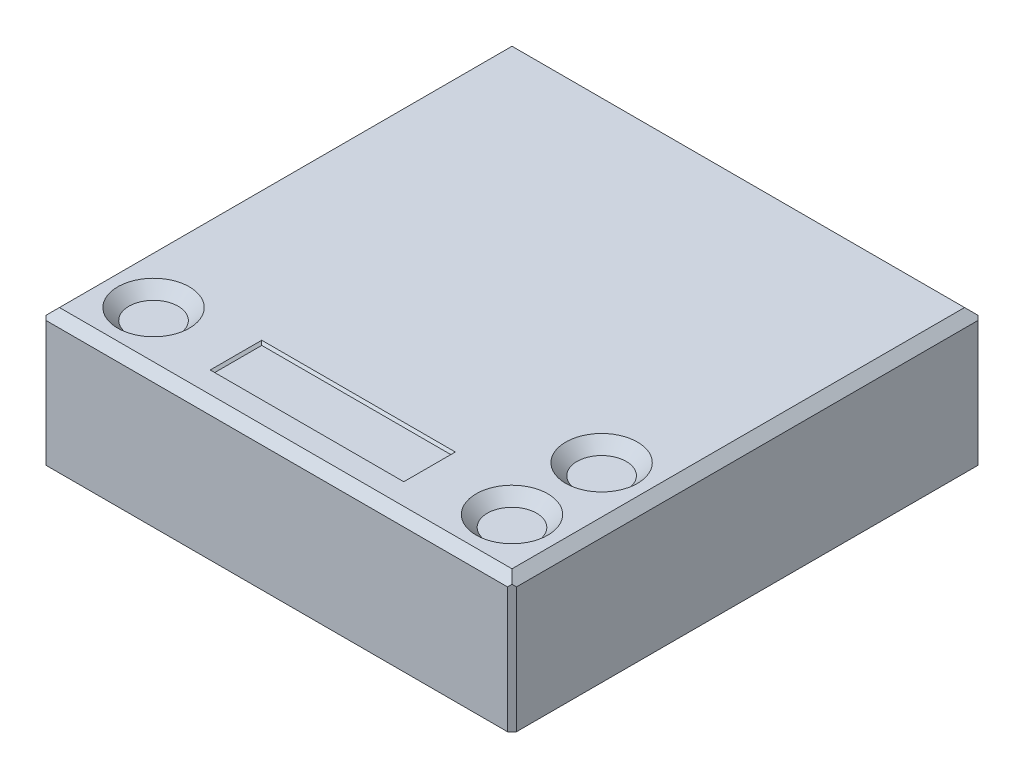
SolidWorks part; units mm, degrees
ref_plane "前视基准面" through (0, 0, 0) normal (0, 0, 1) x (1, 0, 0)
ref_plane "上视基准面" through (0, 0, 0) normal (0, 1, 0) x (1, 0, 0)
ref_plane "右视基准面" through (0, 0, 0) normal (1, 0, 0) x (0, 0, -1)
other "Configuration Table"
sketch "草图1" plane through (0, 0, 0) normal (0, 1, 0) x (1, 0, 0)
  line L0 (-45, 45) -> (45, 45) construction
  line L1 (-50, 50) -> (50, 50)
  line L2 (-50, 50) -> (-50, -50)
  line L3 (-50, -50) -> (50, -50)
  line L4 (50, 50) -> (50, -50)
  line L5 (-50, 50) -> (50, -50) construction
  line L6 (-50, -50) -> (50, 50) construction
  line L7 (-30, -30) -> (30, -30) construction
  line L8 (-40, -40) -> (40, -40) construction
  line L9 (40, -40) -> (40, -20) construction
  line L10 (0, -50) -> (0, -25) construction
  line L11 (28, -31) -> (-24, -31)
  line L12 (28, -31) -> (28, -49)
  line L13 (28, -49) -> (-24, -49)
  line L14 (-24, -31) -> (-24, -49)
  line L15 (0, -25) -> (0, -10) construction
  circle A0 centre (-45, 45) radius 1.75
  circle A1 centre (45, 45) radius 1.75
  circle A2 centre (-30, -30) radius 1.75
  circle A3 centre (30, -30) radius 1.75
  circle A4 centre (-40, -40) radius 5
  circle A5 centre (40, -40) radius 5
  circle A6 centre (40, -20) radius 5
  circle A7 centre (0, -10) radius 2.25
  circle A8 centre (0, -25) radius 2.25
  point P0 (0, 0)
  dimension "D4" = 3.5
  dimension "D8" = 10
  dimension "D13" = 4.5
  dimension "D1" = 100
  dimension "D2" = 100
  dimension "D3" = 5
  dimension "D5" = 20
  dimension "D6" = 10
  dimension "D7" = 20
  dimension "D9" = 52
  dimension "D10" = 18
  dimension "D11" = 1
  dimension "D12" = 22
  dimension "D14" = 25
  dimension "D15" = 15
sketch "草图2" plane through (0, 0, 0) normal (0, 1, 0) x (1, 0, 0)
  line L0 (50, 50) -> (50, -50) construction
  line L1 (-50.5, 50.5) -> (50.5, 50.5)
  line L2 (-50.5, 50.5) -> (-50.5, -50.5)
  line L3 (-50.5, -50.5) -> (50.5, -50.5)
  line L4 (50.5, 50.5) -> (50.5, -50.5)
  line L5 (-50.5, 50.5) -> (50.5, -50.5) construction
  line L6 (-50.5, -50.5) -> (50.5, 50.5) construction
  line L7 (-50, -50) -> (50, -50) construction
  line L9 (-52.5, 52.5) -> (52.5, 52.5)
  line L10 (-52.5, 52.5) -> (-52.5, -52.5)
  line L11 (-52.5, -52.5) -> (52.5, -52.5)
  line L12 (52.5, 52.5) -> (52.5, -52.5)
  line L13 (-52.5, 52.5) -> (52.5, -52.5) construction
  line L14 (-52.5, -52.5) -> (52.5, 52.5) construction
  point P0 (0, 0)
  point P10 (0, 0)
  dimension "D1" = 0.5
  dimension "D2" = 0.5
  dimension "D3" = 2
  dimension "D4" = 2
extrude "凸台-拉伸1" add sketch "草图2" against normal blind 25
extrude "凸台-拉伸2" add sketch "草图2<2>" along normal blind 5 contours L11 L12 L9 L10
sketch "草图2<2>" plane through (0, 0, 0) normal (0, 1, 0) x (1, 0, 0) same geometry as "草图2"
sketch "草图3" plane through (0, 0, 0) normal (0, 1, 0) x (1, 0, 0)
  line L0 (28, -31) -> (28, -49) construction
  line L1 (28, -49) -> (-24, -49) construction
  line L2 (-24, -31) -> (-24, -49) construction
  line L3 (28, -31) -> (-24, -31) construction
  line L4 (28, -31) -> (28, -35)
  line L5 (28, -49) -> (-24, -49)
  line L6 (-24, -31) -> (-24, -49)
  line L7 (28, -31) -> (-24, -31)
  line L8 (28, -35) -> (28, -45) construction
  line L9 (28, -35) -> (30, -35)
  line L10 (28, -35) -> (28, -45) construction
  line L11 (28, -45) -> (30, -45)
  line L12 (30, -35) -> (30, -45)
  line L13 (28, -45) -> (28, -49)
  circle A0 centre (-30, -30) radius 2
  circle A1 centre (-45, 45) radius 2
  circle A2 centre (45, 45) radius 2
  point P17 (-24, -40)
  point P18 (30, -40)
  dimension "D1" = 4
  dimension "D2" = 10
  dimension "D3" = 2
extrude "切除-拉伸1" cut sketch "草图3" along normal blind 3.5
sketch "草图4" plane through (0, 0, 0) normal (0, 1, 0) x (1, 0, 0)
  circle A0 centre (30, -30) radius 1.5
  dimension "D1" = 3
extrude "凸台-拉伸3" add sketch "草图4" against normal blind 3
sketch "草图6" plane through (0, 0, 0) normal (0, 0, 1) x (1, 0, 0)
  line L1 (4.5, -1.5) -> (-4.5, -1.5)
  line L2 (4.5, -1.5) -> (4.5, -5)
  line L3 (4.5, -5) -> (-4.5, -5)
  line L4 (-4.5, -1.5) -> (-4.5, -5)
  line L5 (4.5, -1.5) -> (-4.5, -5) construction
  line L6 (4.5, -5) -> (-4.5, -1.5) construction
  circle A0 centre (-10, -2.25) radius 0.75
  point P0 (0, -3.25)
  dimension "D5" = 1.5
  dimension "D1" = 1.5
  dimension "D2" = 9
  dimension "D3" = 3.5
  dimension "D4" = 10
extrude "切除-拉伸3" cut sketch "草图6" against normal through all
chamfer "倒角3" distance 2 angle 45 4 edges at (0, 5, 52.5) (52.5, 5, 0) (0, 5, -52.5) (-52.5, 5, 0)
chamfer "倒角2" distance 1 angle 45 4 edges at (-52.5, -11, -52.5) (52.5, -11, -52.5) (52.5, -11, 52.5) (-52.5, -11, 52.5)
sketch "草图7" plane through (0, 0, 0) normal (0, 1, 0) x (1, 0, 0)
  circle A0 centre (-40, -40) radius 8
  circle A1 centre (40, -40) radius 8
  circle A2 centre (40, -20) radius 8
  dimension "D1" = 16
extrude "切除-拉伸4" cut sketch "草图7" against normal blind 2.5 from surface starting at face at (0, 5, 0)
chamfer "倒角4" distance 2.5 angle 45 3 edges at (40, 2.5, 48) (40, 2.5, 28) (-40, 2.5, 48)
sketch "草图8" plane through (0, 0, 0) normal (0, 1, 0) x (1, 0, 0)
  line L0 (-40, -40) -> (40, -40) construction
  line L1 (-21.6, -34.25) -> (21.6, -34.25)
  line L2 (-21.6, -34.25) -> (-21.6, -45.75)
  line L3 (-21.6, -45.75) -> (21.6, -45.75)
  line L4 (21.6, -34.25) -> (21.6, -45.75)
  line L5 (-21.6, -34.25) -> (21.6, -45.75) construction
  line L6 (-21.6, -45.75) -> (21.6, -34.25) construction
  point P0 (0, -40)
  dimension "D1" = 43.2
  dimension "D2" = 11.5
extrude "切除-拉伸5" cut sketch "草图8" against normal blind 0.5 from surface starting at face at (-40, 5, 48)
chamfer "倒角5" distance 0.5 angle 45 4 edges at (0, 4.5, 45.75) (21.6, 4.5, 40) (-21.6, 4.5, 40) (0, 4.5, 34.25)
sketch "草图9" plane through (0, 0, 0) normal (0, 1, 0) x (1, 0, 0)
  line L0 (16.1333, -33.3167) -> (16.1333, -26.8167) construction
  line L1 (50.5, 35.4167) -> (35.4167, 35.4167)
  line L2 (50.5, 35.4167) -> (50.5, 39.5)
  line L3 (39.5, 50.5) -> (35.4167, 50.5)
  line L4 (35.4167, 35.4167) -> (35.4167, 50.5)
  line L5 (33.3167, 35.4167) -> (33.3167, 50.5)
  line L6 (33.3167, 35.4167) -> (18.2333, 35.4167)
  line L7 (18.2333, 35.4167) -> (18.2333, 50.5)
  line L8 (33.3167, 50.5) -> (18.2333, 50.5)
  line L9 (16.1333, 35.4167) -> (16.1333, 50.5)
  line L10 (16.1333, 35.4167) -> (1.05, 35.4167)
  line L11 (1.05, 35.4167) -> (1.05, 50.5)
  line L12 (16.1333, 50.5) -> (1.05, 50.5)
  line L13 (-1.05, 35.4167) -> (-1.05, 50.5)
  line L14 (-1.05, 35.4167) -> (-16.1333, 35.4167)
  line L15 (-16.1333, 35.4167) -> (-16.1333, 50.5)
  line L16 (-1.05, 50.5) -> (-16.1333, 50.5)
  line L17 (-18.2333, 35.4167) -> (-18.2333, 50.5)
  line L18 (-18.2333, 35.4167) -> (-33.3167, 35.4167)
  line L19 (-33.3167, 35.4167) -> (-33.3167, 50.5)
  line L20 (-18.2333, 50.5) -> (-33.3167, 50.5)
  line L21 (-35.4167, 35.4167) -> (-35.4167, 50.5)
  line L22 (-35.4167, 35.4167) -> (-50.5, 35.4167)
  line L23 (-50.5, 35.4167) -> (-50.5, 39.5)
  line L24 (-35.4167, 50.5) -> (-39.5, 50.5)
  line L25 (33.3167, 18.2333) -> (33.3167, 33.3167)
  line L26 (33.3167, 18.2333) -> (18.2333, 18.2333)
  line L27 (18.2333, 18.2333) -> (18.2333, 33.3167)
  line L28 (33.3167, 33.3167) -> (18.2333, 33.3167)
  line L29 (16.1333, 18.2333) -> (16.1333, 33.3167)
  line L30 (16.1333, 18.2333) -> (1.05, 18.2333)
  line L31 (1.05, 18.2333) -> (1.05, 33.3167)
  line L32 (16.1333, 33.3167) -> (1.05, 33.3167)
  line L33 (-1.05, 18.2333) -> (-1.05, 33.3167)
  line L34 (-1.05, 18.2333) -> (-16.1333, 18.2333)
  line L35 (-16.1333, 18.2333) -> (-16.1333, 33.3167)
  line L36 (-1.05, 33.3167) -> (-16.1333, 33.3167)
  line L37 (-18.2333, 18.2333) -> (-18.2333, 33.3167)
  line L38 (-18.2333, 18.2333) -> (-33.3167, 18.2333)
  line L39 (-33.3167, 18.2333) -> (-33.3167, 33.3167)
  line L40 (-18.2333, 33.3167) -> (-33.3167, 33.3167)
  line L41 (-35.4167, 18.2333) -> (-35.4167, 33.3167)
  line L42 (-35.4167, 18.2333) -> (-50.5, 18.2333)
  line L43 (-50.5, 18.2333) -> (-50.5, 33.3167)
  line L44 (-35.4167, 33.3167) -> (-50.5, 33.3167)
  line L45 (33.3167, 1.05) -> (33.3167, 16.1333)
  line L46 (33.3167, 1.05) -> (18.2333, 1.05)
  line L47 (18.2333, 1.05) -> (18.2333, 16.1333)
  line L48 (33.3167, 16.1333) -> (18.2333, 16.1333)
  line L49 (16.1333, 1.05) -> (16.1333, 16.1333)
  line L50 (16.1333, 1.05) -> (1.05, 1.05)
  line L51 (1.05, 1.05) -> (1.05, 16.1333)
  line L52 (16.1333, 16.1333) -> (1.05, 16.1333)
  line L53 (-1.05, 1.05) -> (-1.05, 16.1333)
  line L54 (-1.05, 1.05) -> (-16.1333, 1.05)
  line L55 (-16.1333, 1.05) -> (-16.1333, 16.1333)
  line L56 (-1.05, 16.1333) -> (-16.1333, 16.1333)
  line L57 (-18.2333, 1.05) -> (-18.2333, 16.1333)
  line L58 (-18.2333, 1.05) -> (-33.3167, 1.05)
  line L59 (-33.3167, 1.05) -> (-33.3167, 16.1333)
  line L60 (-18.2333, 16.1333) -> (-33.3167, 16.1333)
  line L61 (-35.4167, 1.05) -> (-35.4167, 16.1333)
  line L62 (-35.4167, 1.05) -> (-50.5, 1.05)
  line L63 (-50.5, 1.05) -> (-50.5, 16.1333)
  line L64 (-35.4167, 16.1333) -> (-50.5, 16.1333)
  line L65 (33.3167, -16.1333) -> (33.3167, -1.05)
  line L66 (33.3167, -16.1333) -> (18.2333, -16.1333)
  line L67 (18.2333, -16.1333) -> (18.2333, -1.05)
  line L68 (33.3167, -1.05) -> (18.2333, -1.05)
  line L69 (16.1333, -16.1333) -> (16.1333, -1.05)
  line L70 (16.1333, -16.1333) -> (1.05, -16.1333)
  line L71 (1.05, -16.1333) -> (1.05, -1.05)
  line L72 (16.1333, -1.05) -> (1.05, -1.05)
  line L73 (-1.05, -16.1333) -> (-1.05, -1.05)
  line L74 (-1.05, -16.1333) -> (-16.1333, -16.1333)
  line L75 (-16.1333, -16.1333) -> (-16.1333, -1.05)
  line L76 (-1.05, -1.05) -> (-16.1333, -1.05)
  line L77 (-18.2333, -16.1333) -> (-18.2333, -1.05)
  line L78 (-18.2333, -16.1333) -> (-33.3167, -16.1333)
  line L79 (-33.3167, -16.1333) -> (-33.3167, -1.05)
  line L80 (-18.2333, -1.05) -> (-33.3167, -1.05)
  line L81 (-35.4167, -16.1333) -> (-35.4167, -1.05)
  line L82 (-35.4167, -16.1333) -> (-50.5, -16.1333)
  line L83 (-50.5, -16.1333) -> (-50.5, -1.05)
  line L84 (-35.4167, -1.05) -> (-50.5, -1.05)
  line L85 (33.3167, -33.3167) -> (33.3167, -18.2333) construction
  line L86 (33.3167, -33.3167) -> (18.2333, -33.3167) construction
  line L87 (18.2333, -26.8167) -> (18.2333, -18.2333)
  line L88 (32, -18.2333) -> (18.2333, -18.2333)
  line L89 (16.1333, -26.8167) -> (16.1333, -18.2333)
  line L90 (16.1333, -33.3167) -> (1.05, -33.3167) construction
  line L91 (1.05, -26.8167) -> (1.05, -18.2333)
  line L92 (16.1333, -18.2333) -> (1.05, -18.2333)
  line L93 (-1.05, -26.8167) -> (-1.05, -18.2333)
  line L94 (-1.05, -33.3167) -> (-16.1333, -33.3167) construction
  line L95 (-16.1333, -26.8167) -> (-16.1333, -18.2333)
  line L96 (-1.05, -18.2333) -> (-16.1333, -18.2333)
  line L97 (-18.2333, -26.8167) -> (-18.2333, -18.2333)
  line L98 (-18.2333, -33.3167) -> (-33.3167, -33.3167) construction
  line L99 (-33.3167, -26.8167) -> (-33.3167, -18.2333)
  line L100 (-18.2333, -18.2333) -> (-33.3167, -18.2333)
  line L101 (-35.4167, -32) -> (-35.4167, -18.2333)
  line L102 (-35.4167, -33.3167) -> (-50.5, -33.3167) construction
  line L103 (-50.5, -32) -> (-50.5, -18.2333)
  line L104 (-35.4167, -18.2333) -> (-50.5, -18.2333)
  line L105 (33.3167, -50.5) -> (33.3167, -35.4167) construction
  line L106 (33.3167, -50.5) -> (18.2333, -50.5) construction
  line L107 (18.2333, -50.5) -> (18.2333, -35.4167) construction
  line L108 (33.3167, -35.4167) -> (18.2333, -35.4167) construction
  line L109 (16.1333, -50.5) -> (16.1333, -35.4167) construction
  line L110 (16.1333, -50.5) -> (1.05, -50.5) construction
  line L111 (1.05, -50.5) -> (1.05, -35.4167) construction
  line L112 (16.1333, -35.4167) -> (1.05, -35.4167) construction
  line L113 (-1.05, -50.5) -> (-1.05, -35.4167) construction
  line L114 (-1.05, -50.5) -> (-16.1333, -50.5) construction
  line L115 (-16.1333, -50.5) -> (-16.1333, -35.4167) construction
  line L116 (-1.05, -35.4167) -> (-16.1333, -35.4167) construction
  line L117 (-18.2333, -50.5) -> (-18.2333, -35.4167) construction
  line L118 (-18.2333, -50.5) -> (-33.3167, -50.5) construction
  line L119 (-33.3167, -50.5) -> (-33.3167, -35.4167) construction
  line L120 (-18.2333, -35.4167) -> (-33.3167, -35.4167) construction
  line L121 (-35.4167, -50.5) -> (-35.4167, -35.4167) construction
  line L122 (-35.4167, -50.5) -> (-50.5, -50.5) construction
  line L123 (-50.5, -50.5) -> (-50.5, -35.4167) construction
  line L124 (-35.4167, -35.4167) -> (-50.5, -35.4167) construction
  line L125 (50.5, 18.2333) -> (50.5, 33.3167)
  line L126 (50.5, 18.2333) -> (35.4167, 18.2333)
  line L127 (35.4167, 18.2333) -> (35.4167, 33.3167)
  line L128 (50.5, 33.3167) -> (35.4167, 33.3167)
  line L129 (50.5, 1.05) -> (50.5, 16.1333)
  line L130 (50.5, 1.05) -> (35.4167, 1.05)
  line L131 (35.4167, 1.05) -> (35.4167, 16.1333)
  line L132 (50.5, 16.1333) -> (35.4167, 16.1333)
  line L133 (50.5, -12) -> (50.5, -1.05)
  line L134 (50.5, -16.1333) -> (35.4167, -16.1333) construction
  line L135 (35.4167, -12) -> (35.4167, -1.05)
  line L136 (50.5, -1.05) -> (35.4167, -1.05)
  line L137 (50.5, -33.3167) -> (50.5, -18.2333) construction
  line L138 (50.5, -33.3167) -> (35.4167, -33.3167) construction
  line L139 (35.4167, -33.3167) -> (35.4167, -18.2333) construction
  line L140 (50.5, -18.2333) -> (35.4167, -18.2333) construction
  line L141 (50.5, -50.5) -> (50.5, -35.4167) construction
  line L142 (50.5, -50.5) -> (35.4167, -50.5) construction
  line L143 (35.4167, -50.5) -> (35.4167, -35.4167) construction
  line L144 (50.5, -35.4167) -> (35.4167, -35.4167) construction
  line L145 (-50.5, 50.5) -> (-50.5, -50.5) construction
  line L146 (-50.5, -50.5) -> (50.5, -50.5) construction
  line L147 (50.5, -50.5) -> (50.5, 50.5) construction
  line L148 (32, -26.8167) -> (18.2333, -26.8167)
  line L149 (32, -26.8167) -> (32, -18.2333)
  line L150 (50.5, -12) -> (35.4167, -12)
  line L151 (50.5, -16.1333) -> (50.5, -12) construction
  line L152 (35.4167, -16.1333) -> (35.4167, -12) construction
  line L153 (18.2333, -33.3167) -> (18.2333, -26.8167) construction
  line L154 (18.2333, -26.8167) -> (16.1333, -26.8167) construction
  line L155 (16.1333, -26.8167) -> (1.05, -26.8167)
  line L156 (1.05, -33.3167) -> (1.05, -26.8167) construction
  line L157 (1.05, -26.8167) -> (-1.05, -26.8167) construction
  line L158 (-1.05, -26.8167) -> (-16.1333, -26.8167)
  line L159 (-1.05, -33.3167) -> (-1.05, -26.8167) construction
  line L160 (-16.1333, -33.3167) -> (-16.1333, -26.8167) construction
  line L161 (-16.1333, -26.8167) -> (-18.2333, -26.8167) construction
  line L162 (-18.2333, -26.8167) -> (-33.3167, -26.8167)
  line L163 (-18.2333, -33.3167) -> (-18.2333, -26.8167) construction
  line L164 (-33.3167, -33.3167) -> (-33.3167, -26.8167) construction
  line L165 (-35.4167, -32) -> (-50.5, -32)
  line L166 (-35.4167, -33.3167) -> (-35.4167, -32) construction
  line L167 (-50.5, -33.3167) -> (-50.5, -32) construction
  line L168 (33.3167, -18.2333) -> (32, -18.2333) construction
  line L169 (50.5, 50.5) -> (45, 50.5) construction
  line L170 (50.5, 45) -> (50.5, 50.5) construction
  line L171 (-45, 50.5) -> (-50.5, 50.5) construction
  line L172 (-50.5, 45) -> (-50.5, 50.5) construction
  line L173 (-39.5, 45) -> (-39.5, 50.5)
  line L174 (-45, 39.5) -> (-50.5, 39.5)
  line L175 (39.5, 45) -> (39.5, 50.5)
  line L176 (45, 39.5) -> (50.5, 39.5)
  line L177 (-39.5, 50.5) -> (-45, 50.5) construction
  line L178 (-50.5, 39.5) -> (-50.5, 45) construction
  line L179 (45, 50.5) -> (39.5, 50.5) construction
  line L180 (50.5, 39.5) -> (50.5, 45) construction
  circle A0 centre (-40, -40) radius 8 construction
  arc A1 (39.5, 45) -> (45, 39.5) centre (45, 45) ccw
  circle A2 centre (40, -20) radius 8 construction
  arc A3 (-45, 39.5) -> (-39.5, 45) centre (-45, 45) ccw
  arc A4 (50.5, 45) -> (45, 50.5) centre (45, 45) ccw construction
  arc A5 (-45, 50.5) -> (-50.5, 45) centre (-45, 45) ccw construction
  arc A6 (-39.5, 45) -> (-45, 50.5) centre (-45, 45) ccw construction
  arc A7 (-50.5, 45) -> (-45, 39.5) centre (-45, 45) ccw construction
  arc A8 (45, 50.5) -> (39.5, 45) centre (45, 45) ccw construction
  arc A9 (45, 39.5) -> (50.5, 45) centre (45, 45) ccw construction
  dimension "D1" = 6
  dimension "D2" = 6
  dimension "D3" = 15.0833
  dimension "D4" = 15.0833
  dimension "D5" = 6.5
extrude "切除-拉伸6" cut sketch "草图9" along normal blind 3.5 from surface starting at face at (30, 0, 31.5)
sketch "草图11" plane through (0, 0, 0) normal (0, 1, 0) x (1, 0, 0)
  line L0 (-1.05, -1.05) -> (-1.05, -16.1333) construction
  line L1 (1.05, -23.1833) -> (-1.05, -23.1833)
  line L2 (1.05, -23.1833) -> (1.05, -26.8167)
  line L3 (1.05, -26.8167) -> (-1.05, -26.8167)
  line L4 (-1.05, -23.1833) -> (-1.05, -26.8167)
  line L5 (1.05, -23.1833) -> (-1.05, -26.8167) construction
  line L6 (1.05, -26.8167) -> (-1.05, -23.1833) construction
  line L7 (1.05, -8.01) -> (-1.05, -8.01)
  line L8 (1.05, -8.01) -> (1.05, -11.99)
  line L9 (1.05, -11.99) -> (-1.05, -11.99)
  line L10 (-1.05, -8.01) -> (-1.05, -11.99)
  line L11 (1.05, -8.01) -> (-1.05, -11.99) construction
  line L12 (1.05, -11.99) -> (-1.05, -8.01) construction
  circle A0 centre (0, -10) radius 2.25 construction
  point P0 (0, -25)
  point P7 (0, -10)
extrude "切除-拉伸8" cut sketch "草图11" along normal up to surface (3.5 mm away) from surface up to face at (-8.5917, 3.5, 8.5917) starting at face at (30, 0, 31.5)
